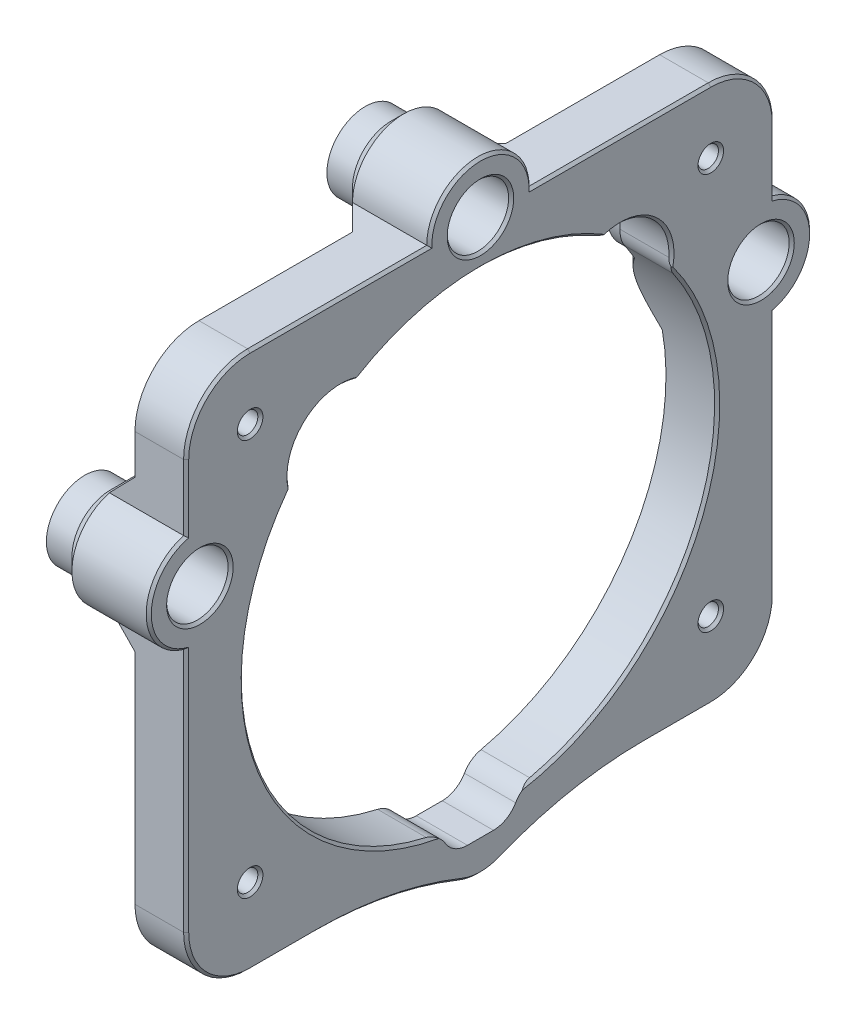
SolidWorks part; units mm, degrees
ref_plane "前视基准面" through (0, 0, 0) normal (0, 0, 1) x (1, 0, 0)
ref_plane "上视基准面" through (0, 0, 0) normal (0, 1, 0) x (1, 0, 0)
ref_plane "右视基准面" through (0, 0, 0) normal (1, 0, 0) x (0, 0, -1)
other "Configuration Table"
sketch "草图1" plane through (0, 0, 0) normal (1, 0, 0) x (0, 0, -1)
  line L1 (0, 0) -> (46, 0)
  line L2 (0, 0) -> (0, -41)
  line L3 (0, -41) -> (46, -41)
  line L4 (46, 0) -> (46, -41)
  circle A0 centre (5, -5) radius 0.8
  circle A1 centre (41, -5) radius 0.8
  circle A2 centre (5, -36) radius 0.8
  circle A3 centre (41, -36) radius 0.8
  dimension "D1" = 1.6
  dimension "D2" = 1.6
  dimension "D3" = 1.6
  dimension "D4" = 1.6
  dimension "D7" = 46
  dimension "D8" = 41
  dimension "D5" = 5
  dimension "D6" = 5
  dimension "D9" = 5
  dimension "D10" = 5
  dimension "D11" = 5
  dimension "D12" = 5
  dimension "D13" = 5
  dimension "D14" = 5
extrude "凸台-拉伸1" add sketch "草图1" along normal blind 4
sketch "草图2" plane through (0, 0, 0) normal (-1, 0, 0) x (0, 0, 1)
  line L1 (-46, 0) -> (0, 0) construction
  circle A0 centre (-44.925, -14) radius 4
  circle A1 centre (-1.075, -14) radius 4
  circle A2 centre (-23, 0) radius 4
  point P8 (-23, 0)
  dimension "D7" = 8
  dimension "D8" = 8
  dimension "D9" = 8
  dimension "D2" = 0
  dimension "D3" = 14
  dimension "D4" = 14
  dimension "D5" = 43.85
  dimension "D6" = 21.925
extrude "凸台-拉伸2" add sketch "草图2" against normal blind 4
sketch "草图3" plane through (0, 0, 0) normal (-1, 0, 0) x (0, 0, 1)
  circle A0 centre (-44.925, -14) radius 3
  circle A1 centre (-23, 0) radius 3
  circle A2 centre (-1.075, -14) radius 3
  dimension "D1" = 6
  dimension "D2" = 6
  dimension "D3" = 6
extrude "凸台-拉伸3" add sketch "草图3" along normal blind 5
sketch "草图4" plane through (-5, 0, 0) normal (-1, 0, 0) x (0, 0, 1)
  circle A0 centre (-44.925, -14) radius 1.6
  circle A1 centre (-23, 0) radius 1.6
  circle A2 centre (-1.075, -14) radius 1.6
  dimension "D1" = 3.2
  dimension "D2" = 3.2
  dimension "D3" = 3.2
extrude "切除-拉伸2" cut sketch "草图4" against normal through all
sketch "草图5" plane through (4, 0, 0) normal (1, 0, 0) x (0, 0, -1)
  circle A0 centre (1.075, -14) radius 2.4
  circle A1 centre (23, 0) radius 2.4
  circle A2 centre (44.925, -14) radius 2.4
  dimension "D1" = 4.8
  dimension "D2" = 4.8
  dimension "D3" = 4.8
extrude "切除-拉伸3" cut sketch "草图5" against normal blind 4.2
chamfer "倒角2" distance 3 angle 45 3 edges at (0, -14, -4.075) (0, 0, -26) (0, -14, -47.925)
sketch "草图6" plane through (0, 0, 0) normal (-1, 0, 0) x (0, 0, 1)
  circle A0 centre (-23, -22) radius 18.5
  dimension "D1" = 37
extrude "切除-拉伸4" cut sketch "草图6" against normal through all and the other way through all
sketch "草图7" plane through (0, -41, 0) normal (0, -1, 0) x (-1, 0, 0)
  line L1 (0, 0) -> (-4, 0)
  line L2 (0, 0) -> (0, 46)
  line L3 (0, 46) -> (-4, 46)
  line L4 (-4, 0) -> (-4, 46)
extrude "凸台-拉伸4" add sketch "草图7" along normal blind 1
fillet "圆角2" radius 5 4 edges at (2, 0, 0) (2, 0, -46) (2, -42, -46) (2, -42, 0)
sketch "草图8" plane through (0, 0, 0) normal (-1, 0, 0) x (0, 0, 1)
  circle A0 centre (-33.925, -10) radius 4
  circle A1 centre (-12.075, -10) radius 4
  circle A2 centre (-44.925, -14) radius 1.6 construction
  circle A3 centre (-1.075, -14) radius 1.6 construction
  dimension "D1" = 8
  dimension "D2" = 8
  dimension "D6" = 11
  dimension "D3" = 4
  dimension "D4" = 4
  dimension "D5" = 11
extrude "切除-拉伸5" cut sketch "草图8" against normal through all
sketch "草图9" plane through (0, 0, 0) normal (-1, 0, 0) x (0, 0, 1)
  line L0 (-26.7081, -42) -> (-19.2919, -42)
  line L1 (-5, -42) -> (-41, -42) construction
  arc A0 (-26.7081, -42) -> (-19.2919, -42) centre (-23, -40.5) ccw
  arc A1 (-41.2046, -18.7073) -> (-4.7954, -18.7073) centre (-23, -22) ccw construction
  dimension "D1" = 8
extrude "凸台-拉伸5" add sketch "草图9" against normal blind 4
fillet "圆角3" radius 30 2 edges at (2, -42, -19.2919) (2, -42, -26.7081)
chamfer "倒角3" distance 0.2 angle 45 29 edges at (4, -36, -41.8) (4, -5, -41.8) (4, -5, -5.8) (4, -36, -5.8) (4, 4, -23) (4, 0, -34) (4, -1.4645, -44.5355) (4, -7.5736, -46) (4, -14, -48.925) (4, -27.4264, -46) (4, -40.5355, -44.5355) (4, -42, -7.6018) (4, -42, -38.3982) (4, -40.5355, -1.4645) (4, -27.4264, 0) (4, -14, 2.925) (4, -7.5736, 0) (4, -1.4645, -1.4645) (4, 0, -12) (4, -14, -47.325) (4, 0, -25.4) (4, -14, -3.475) (4, -3.5, -23) (4, -7.0422, -9.3822) (4, -40.5, -23) (4, -7.0422, -36.6178) (4, -42.5566, -30.0442) (4, -44.5, -23) (4, -42.5566, -15.9558)
sketch "草图10" plane through (0, 0, 0) normal (-1, 0, 0) x (0, 0, 1)
  line L0 (-5, -42) -> (-10.2035, -42) construction
  line L1 (-26, -38.5149) -> (-20, -38.5149)
  line L2 (-26, -38.5149) -> (-26, -42)
  line L3 (-26, -42) -> (-20, -42)
  line L4 (-20, -38.5149) -> (-20, -42)
  arc A0 (-24.5055, -44.2059) -> (-21.4945, -44.2059) centre (-23, -40.5) ccw construction
  point P4 (-23, -42)
  point P8 (-23, -44.5)
  dimension "D1" = 6
  dimension "D2" = 0
  dimension "D3" = 0
extrude "切除-拉伸6" cut sketch "草图10" against normal through all
fillet "圆角4" radius 2 2 edges at (2, -42, -20) (2, -42, -26)
fillet "圆角5" radius 2 6 edges at (1.9, -10.9228, -37.8171) (1.9, -6.2113, -32.642) (1.9, -6.2113, -13.358) (1.9, -10.9228, -8.1829) (1.9, -40.2551, -20) (1.9, -40.2551, -26)
equation "\"D7@草图1\"=36+10"
equation "\"D8@草图1\"=31+10"
equation "\"D6@草图2\"=\"D5@草图2\"/2"
